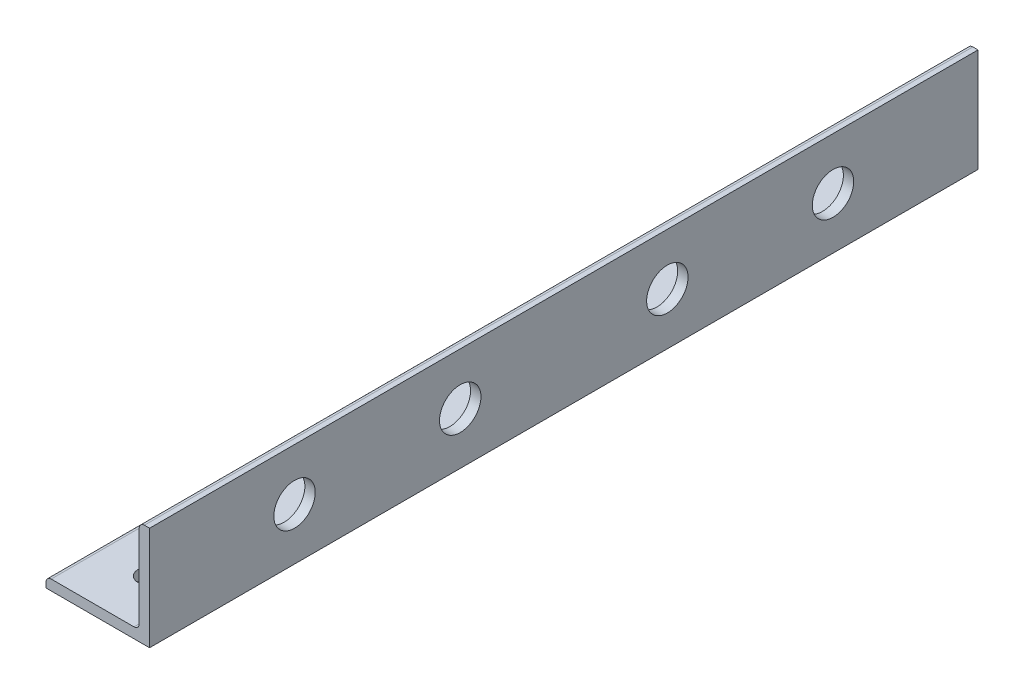
SolidWorks part; units mm, degrees
ref_plane "Front Plane" through (0, 0, 0) normal (0, 0, 1) x (1, 0, 0)
ref_plane "Top Plane" through (0, 0, 0) normal (0, 1, 0) x (1, 0, 0)
ref_plane "Right Plane" through (0, 0, 0) normal (1, 0, 0) x (0, 0, -1)
sketch "Sketch2" plane through (0, 0, 0) normal (0, 0, 1) x (1, 0, 0)
  line L0 (-7.9375, 0) -> (7.9375, 0)
  line L1 (7.9375, 0) -> (7.9375, 15.875)
  line L2 (7.9375, 15.875) -> (6.35, 15.875) construction
  line L3 (6.35, 15.0813) -> (6.35, 2.3812)
  line L4 (5.5563, 1.5875) -> (-7.1438, 1.5875)
  line L5 (-7.9375, 0) -> (-7.9375, 1.5875) construction
  line L6 (7.1438, 15.875) -> (7.9375, 15.875)
  line L7 (-7.9375, 0.7937) -> (-7.9375, 0)
  arc A0 (6.35, 15.0813) -> (7.1438, 15.875) centre (7.1438, 15.0813) cw
  arc A1 (-7.9375, 0.7937) -> (-7.1438, 1.5875) centre (-7.1438, 0.7937) cw
  arc A2 (6.35, 2.3812) -> (5.5563, 1.5875) centre (5.5563, 2.3812) cw
  dimension "Vert" = 15.875
  dimension "Horz" = 15.875
  dimension "Thickness" = 1.5875
extrude "Boss-Extrude1" add sketch "Sketch2" along normal mid plane 127
ref_plane "Contact Plane 1" through (0, 1.5875, 0) normal (0, 1, 0) x (1, 0, 0)
ref_plane "Contact Plane 2" through (6.35, 0, 0) normal (-1, 0, 0) x (0, 0, 1)
sketch "Sketch3" plane through (7.9375, 0, 0) normal (1, 0, 0) x (0, 0, -1)
  line L0 (41.275, 7.9375) -> (-41.275, 7.9375) construction
  line L1 (-63.5, 15.875) -> (63.5, 15.875) construction
  line L2 (-63.5, 15.875) -> (-63.5, 0) construction
  line L3 (-63.5, 0) -> (63.5, 0) construction
  line L4 (63.5, 15.875) -> (63.5, 0) construction
  circle A0 centre (-41.275, 7.9375) radius 3.175
  circle A1 centre (41.275, 7.9375) radius 3.175
  circle A2 centre (-15.875, 7.9375) radius 3.175
  circle A3 centre (15.875, 7.9375) radius 3.175
  point P6 (63.5, 7.9375)
  point P10 (0, 15.875)
  point P13 (0, 7.9375)
  dimension "D1" = 6.35
  dimension "D2" = 82.55
  dimension "D3" = 25.4
  dimension "D4" = 25.4
extrude "Cut-Extrude1" cut sketch "Sketch3" against normal through all contours A0 | A1 | A2 | A3 region at (7.9375, 7.9375, 41.275) region at (7.9375, 7.9375, -41.275) region at (7.9375, 7.9375, 15.875) region at (7.9375, 7.9375, -15.875)
sketch "Sketch4" plane through (0, 0, 0) normal (0, -1, 0) x (1, 0, 0)
  line L0 (0, 55.5625) -> (0, -55.5625)
  line L1 (-7.9375, -63.5) -> (7.9375, -63.5) construction
  line L3 (7.9375, 63.5) -> (7.9375, -63.5) construction
  line L4 (0, 55.5625) -> (7.9375, 55.5625)
  line L5 (7.9375, 55.5625) -> (0, 55.5625)
  line L6 (0, 55.5625) -> (0, 63.5)
  line L7 (-7.9375, 63.5) -> (7.9375, 63.5) construction
  circle A0 centre (0, -55.5625) radius 1.75
  circle A1 centre (0, 55.5625) radius 1.75
  point P4 (0, 0)
  point P9 (0, -63.5)
  point P14 (7.9375, 0)
  dimension "D1" = 3.5
extrude "Cut-Extrude2" cut sketch "Sketch4" against normal through all contours L6 A1 L0 | L4 A1 L6 | L0 A1 L4 | A0 region at (0.7427, 0, 54.8198) region at (0.7427, 0, 56.3052) region at (-0.7427, 0, 55.5625) region at (1.2024, 0, -54.3601)
